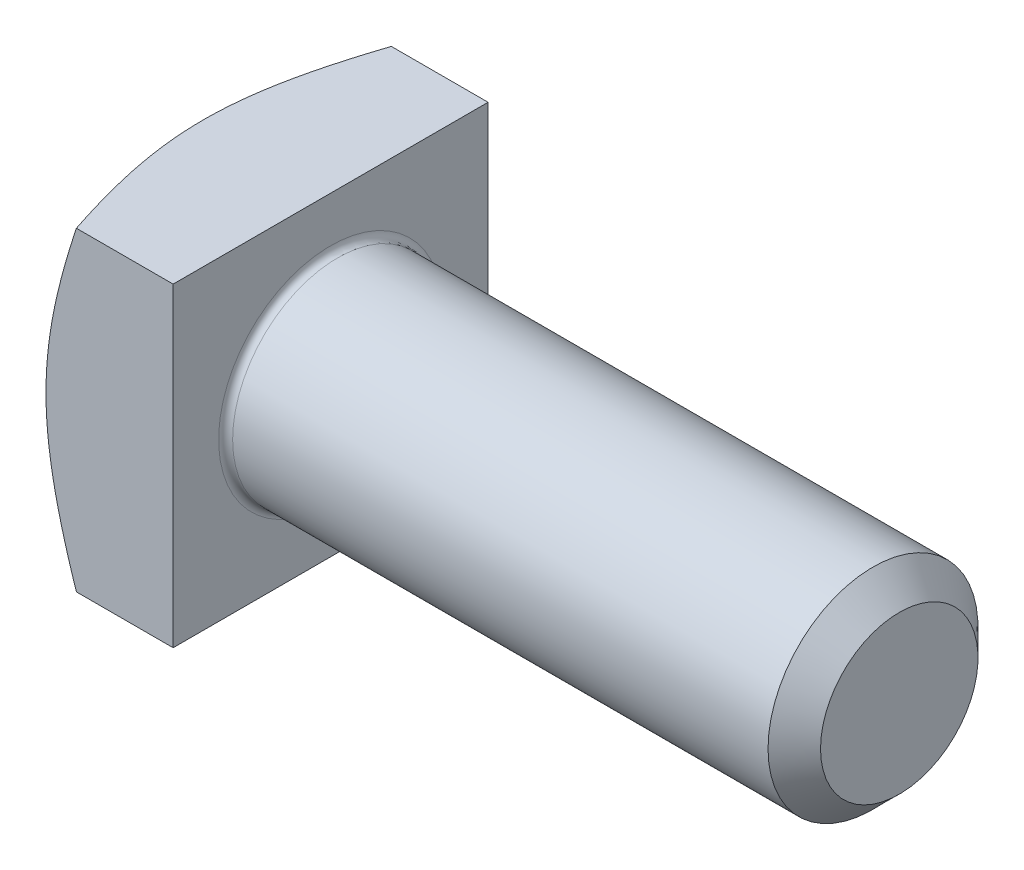
SolidWorks part; units mm, degrees
ref_plane "Front Plane" through (0, 0, 0) normal (0, 0, 1) x (1, 0, 0)
ref_plane "Top Plane" through (0, 0, 0) normal (0, 1, 0) x (1, 0, 0)
ref_plane "Right Plane" through (0, 0, 0) normal (1, 0, 0) x (0, 0, -1)
sketch "BaseHeadSke" plane through (0, 0, 0) normal (1, 0, 0) x (0, 0, -1)
  line L0 (18, 18) -> (-18, -18) construction
  line L2 (18, 18) -> (-18, 18)
  line L3 (-18, 18) -> (-18, -18)
  line L5 (-18, -18) -> (18, -18)
  line L6 (18, -18) -> (18, 18)
  dimension "Width_flats" = 36
extrude "BaseHead" add sketch "BaseHeadSke" along normal blind 15
sketch "BodySke" plane through (0, 0, 0) normal (0, 0, 1) x (1, 0, 0)
  line L0 (0, 0) -> (80, 0)
  line L1 (80, 0) -> (80, 12)
  line L2 (51.3878, 10.352) -> (123.0174, 10.352) construction
  line L3 (80, 12) -> (0, 12)
  line L4 (0, 12) -> (0, 0)
  line L5 (15, 18) -> (15, -18) construction
  line L6 (0, 0) -> (159.3976, 0) construction
  line L7 (26, -84.3176) -> (26, 77.7215) construction
  line L8 (77, -21.5941) -> (77, 39.2994) construction
  dimension "Minor_dia" = 20.704
  dimension "Thread_length" = 54
  dimension "Length" = 65
revolve "BaseBody" add sketch "BodySke" angle 360 about L6
cosmetic thread "ThreadCosmetic" [suppressed] parameters "Thread_length"=54, "Thread_minor"=20.704
sketch "ChamferEndSke" plane through (0, 0, 0) normal (0, 1, 0) x (1, 0, 0)
  line L0 (77, -12) -> (80, -9)
  line L1 (80, -9) -> (80, -12)
  line L2 (80, -12) -> (77, -12)
  line L4 (80, -12) -> (80, 12) construction
  line L5 (15, -12) -> (80, -12) construction
  line L6 (0, 0) -> (120.8692, 0) construction
  dimension "Ang" = 45
revolve "ChamferEnd" cut sketch "ChamferEndSke" angle 360 about L6
sketch "CutEndSke" plane through (80, 0, 0) normal (1, 0, 0) x (0, 0, -1)
  circle A0 centre (0, 0) radius 12 construction
  circle A1 centre (0, 0) radius 12
extrude "CutEnd" [suppressed] cut sketch "CutEndSke" against normal blind 3
dome "RoundEnd" [suppressed] faces to dome 1 distance 3 parameters "D1"=3
sketch "HeadChamferSke" plane through (0, 0, 0) normal (0, 0, 1) x (1, 0, 0)
  line L0 (15, 49.1676) -> (0, 49.1676)
  line L1 (0, 49.1676) -> (0, 17)
  line L2 (0, 17) -> (15, 49.1676)
  line L3 (0, 0) -> (120.9185, 0) construction
  dimension "D1" = 25
  dimension "Head_chamfer" = 34
revolve "HeadChamfer" cut sketch "HeadChamferSke" angle 360 about L3
fillet "Fillet" radius 0.8 1 edges at (15, 0, -12)
sketch "ThdSchSke" plane through (0, 0, 0) normal (0, 0, 1) x (1, 0, 0)
  line L0 (74.5485, 13.9029) -> (74.5485, 12)
  line L1 (74.5485, 12) -> (75.5, 10.352)
  line L2 (75.5, 10.352) -> (76.4515, 12)
  line L3 (76.4515, 12) -> (76.4515, 13.9029)
  line L4 (76.4515, 13.9029) -> (74.5485, 13.9029)
  line L6 (0, 0) -> (141.9934, 0) construction
  line L8 (80, -61.7617) -> (80, 46.755) construction
  line L9 (15, -18) -> (15, 18) construction
  dimension "D2" = 20.704
  dimension "D3" = 24
  dimension "Length" = 65
  dimension "Advance" = 4.5
revolve "ThreadSchematic" [suppressed] cut sketch "ThdSchSke" angle 360 about L6
pattern_linear "ThdSchPat" [suppressed] count 18 spacing 3 along (-1, 0, 0) of bodies 107
equation "\"Thread_minor@ThreadCosmetic\" = \"Minor_dia@BodySke\""
equation "\"Thread_length@ThreadCosmetic\" = \"Thread_length@BodySke\""
equation "\"D1@CutEnd\" = \"Chamfer_width@ChamferEndSke\""
equation "\"D1@RoundEnd\" = \"Chamfer_width@ChamferEndSke\""
equation "\"D2@ThdSchSke\" = \"Minor_dia@BodySke\""
equation "\"D3@ThdSchSke\" = \"Diameter@BodySke\""
equation "\"Length@ThdSchSke\" = \"Length@BodySke\""
equation "\"Advance@ThdSchSke\" = \"Advance@BodySke\"*1.5"
equation "\"D3@ThdSchPat\" = \"Advance@BodySke\""
equation "\"D1@ThdSchPat\" =  int( \"Thread_length@BodySke\"/\"Advance@BodySke\" )"
